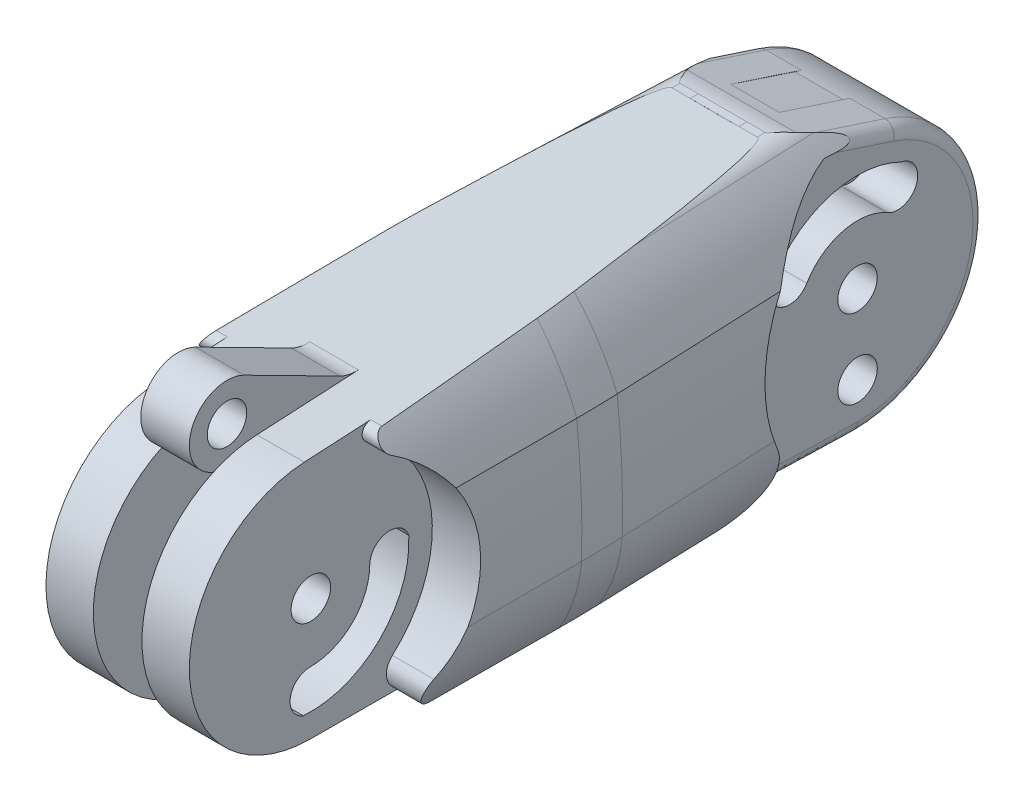
SolidWorks part; units mm, degrees
other "Camera1"
other "Camera2"
ref_plane "Front Plane" through (0, 0, 0) normal (0, 0, 1) x (1, 0, 0)
ref_plane "Top Plane" through (0, 0, 0) normal (0, 1, 0) x (1, 0, 0)
ref_plane "Right Plane" through (0, 0, 0) normal (1, 0, 0) x (0, 0, -1)
sketch "Sketch1" plane through (0, 0, 0) normal (1, 0, 0) x (0, 0, -1)
  line L0 (6.4997, -0.0595) -> (0, 0) construction
  line L1 (0, 0) -> (-0.0595, -6.4997) construction
  line L2 (0, 0) -> (11.6209, -0.1064) construction
  line L3 (39.3989, 2.8894) -> (44.9981, -0.4119) construction
  line L4 (44.9981, -0.4119) -> (48.2995, 5.1872) construction
  line L5 (-0.5384, 9.9855) -> (39.1425, 12.125)
  line L6 (41.3318, 11.8361) -> (48.2642, 9.5672)
  circle A0 centre (0, 0) radius 1.625
  circle A1 centre (44.9981, -0.4119) radius 1.625
  arc A2 (-1.6942, -6.2753) -> (6.3053, 1.579) centre (0, 0) ccw construction
  arc A3 (49.603, 4.1756) -> (38.7481, 1.3732) centre (44.9981, -0.4119) ccw construction
  arc A4 (-0.0444, -4.8498) -> (4.8498, -0.0444) centre (0, 0) ccw
  arc A5 (-0.6238, -8.0502) -> (8.0603, 0.4763) centre (0, 0) ccw
  arc A6 (8.0603, 0.4763) -> (4.8498, -0.0444) centre (6.4997, -0.0595) ccw
  arc A7 (-0.0444, -4.8498) -> (-0.6238, -8.0502) centre (-0.0595, -6.4997) ccw
  arc A8 (47.4615, 3.7659) -> (40.8203, 2.0514) centre (44.9981, -0.4119) ccw
  arc A9 (48.6157, 6.8066) -> (37.7795, 3.2057) centre (44.9981, -0.4119) ccw
  arc A10 (37.7795, 3.2057) -> (40.8203, 2.0514) centre (39.3989, 2.8894) ccw
  arc A11 (47.4615, 3.7659) -> (48.6157, 6.8066) centre (48.2995, 5.1872) ccw
  arc A12 (44.9981, -10.9119) -> (48.2642, 9.5672) centre (44.9981, -0.4119) ccw
  arc A13 (-0.5384, 9.9855) -> (0, -10) centre (0, 0) ccw
  arc A14 (39.1425, 12.125) -> (41.3318, 11.8361) centre (39.4655, 6.1337) cw
  spline S0 degree 3 poles (44.9981, -10.9119) (37.0207, -10.7959) (25.9467, -10) (0, -10) knots 0 0 0 0 1 1 1 1
  point P43 (40.2642, 12.1855)
  dimension "D2" = 3.25
  dimension "D3" = 13
  dimension "D4" = 1.65
  dimension "D5" = 10.5
  dimension "D10" = 20
  dimension "D13" = 6
  dimension "D1" = 45
  dimension "D6" = 90
  dimension "D7" = 0
  dimension "D8" = 90
  dimension "D9" = 30
  dimension "D11" = 2.2
  dimension "D12" = 8
extrude "Boss-Extrude1" add sketch "Sketch1" along normal mid plane 20
sketch "Sketch3" plane through (-10, 0, 0) normal (-1, 0, 0) x (0, 0, 1)
  circle A0 centre (-44.9981, -0.4119) radius 11
  dimension "D1" = 22
extrude "Cut-Extrude1" cut sketch "Sketch3" against normal blind 4.1
mirror "Mirror1" about plane through (0, 0, 0) normal (1, 0, 0) of "Cut-Extrude1"
sketch "Sketch5" plane through (0, 0, 0) normal (1, 0, 0) x (0, 0, -1)
  circle A0 centre (0, 0) radius 10
  dimension "D1" = 20
extrude "Cut-Extrude3" cut sketch "Sketch5" against normal mid plane 12
sketch "Sketch6" plane through (0, 0, 0) normal (1, 0, 0) x (0, 0, -1)
  line L20 (39.2501, 10.1279) -> (55.8409, 11.0225)
  line L21 (55.8409, 11.0225) -> (57.0278, -10.9915)
  line L22 (39.2501, 10.1279) -> (-0.4307, 7.9884)
  line L23 (47.6421, 7.6664) -> (40.7097, 9.9353)
  line L24 (39.2501, 10.1279) -> (-0.4307, 7.9884)
  line L26 (57.0278, -10.9915) -> (-8, -10.9915)
  line L27 (-8, -10.9915) -> (-8, 0)
  arc A6 (40.7097, 9.9353) -> (39.2501, 10.1279) centre (39.4655, 6.1337) ccw
  arc A7 (45.0119, -8.9119) -> (47.6421, 7.6664) centre (44.9981, -0.4119) ccw
  arc A8 (-0.4307, 7.9884) -> (0, -8) centre (0, 0) ccw
  arc A11 (-0.4307, 7.9884) -> (-8, 0) centre (0, 0) ccw
  spline S8 degree 3 poles (-629.4347, 769.0527) (-440.0939, -94.2718) (-207.9713, -3.0744) (26.2611, -8.3178) (30.0115, -8.4293) (35.6362, -8.6246) (37.5109, -8.6944) (99.686, -10.84) (160.1173, -8.7801) (251.4508, 969.4985) knots -14.861079 -14.861079 -14.861079 -14.861079 0.5 0.5 0.75 0.75 0.875 0.875 4.89518 4.89518 4.89518 4.89518 only from (0, -8) to (45.0119, -8.9119)
  dimension "D1" = 2
extrude "Cut-Extrude4" cut sketch "Sketch6" against normal mid plane 4
sketch "Sketch10" plane through (0, 0, 0) normal (0, 0, 1) x (1, 0, 0)
  line L0 (0, 12.123) -> (-4.3435, 12.1247)
  line L9 (10, 12.125) -> (-10, 12.125) construction
  line L11 (-7.5, -11) -> (-12.998, -11)
  line L12 (-12.998, -11) -> (-12.998, 14.3465)
  line L13 (-12.998, 14.3465) -> (0, 14.3465)
  line L14 (0, 14.3465) -> (0, 12.123)
  arc A2 (-5.8246, 11.4695) -> (-9.5, 5.5) centre (8.2393, -1.3058) ccw
  arc A3 (-9.5, 5.5) -> (-9.9, -4.5) centre (70.0795, -2.6912) ccw
  arc A4 (-9.9, -4.5) -> (-7.5, -11) centre (3.0542, -3.41) ccw
  arc A5 (-4.3435, 12.1247) -> (-5.8246, 11.4695) centre (-4.3442, 10.1247) ccw
  point P14 (-10, 9.9855)
  point P22 (-5.2, 12.125)
  dimension "D2" = 5.5
  dimension "D1" = 5.2
  dimension "D4" = 19
  dimension "D7" = 80
  dimension "D10" = 13
  dimension "D11" = 2
  dimension "D3" = 9.5
  dimension "D5" = 9.9
  dimension "D6" = 4.5
  dimension "D8" = 7.5
  dimension "D9" = 11
  dimension "D12" = 9.9
sketch "Sketch20" plane through (0, 0, 0) normal (0, 1, 0) x (1, 0, 0)
  line L0 (-10, -10) -> (-10, 18.2865)
  line L1 (-10, 39.1425) -> (-10, -0.5384) construction
  line L2 (-9.9266, 21.7119) -> (-8.5, 55)
  arc A0 (-10, 18.2865) -> (-9.9266, 21.7119) centre (70, 18.2865) cw
  point P9 (-10, 20)
  dimension "D4" = 80
  dimension "D1" = 1.5
  dimension "D2" = 20
  dimension "D3" = 55
sweep "Sweep1" add profiles "Sketch10" path "Sketch20"
mirror "Mirror4" about plane through (0, 14.3465, -18.2865) normal (1, 0, 0) of bodies 117
combine bodies "Combine2" operation type subtract main body 107 bodies to subtract 120 117
sketch "Sketch15" plane through (-6, 0, 0) normal (1, 0, 0) x (0, 0, -1)
  circle A0 centre (0, 0) radius 1.625 construction
  circle A1 centre (0, 0) radius 1.625
  arc A2 (-0.0444, -4.8498) -> (-0.6238, -8.0502) centre (-0.0595, -6.4997) ccw construction
  arc A3 (0, -10) -> (-0.5384, 9.9855) centre (0, 0) ccw
  arc A5 (0, -10) -> (-0.5384, 9.9855) centre (0, 0) ccw
  arc A8 (8.0603, 0.4763) -> (4.8498, -0.0444) centre (6.4997, -0.0595) ccw construction
  arc A9 (-0.0444, -4.8498) -> (4.8498, -0.0444) centre (0, 0) ccw construction
  arc A14 (-0.6238, -8.0502) -> (8.0603, 0.4763) centre (0, 0) ccw construction
  arc A15 (-0.5384, 9.9855) -> (0, -10) centre (0, 0) ccw
  arc A17 (-0.0444, -4.8498) -> (-0.6238, -8.0502) centre (-0.0595, -6.4997) ccw
  arc A18 (8.0603, 0.4763) -> (4.8498, -0.0444) centre (6.4997, -0.0595) ccw
  arc A19 (-0.0444, -4.8498) -> (4.8498, -0.0444) centre (0, 0) ccw
  arc A20 (-0.6238, -8.0502) -> (8.0603, 0.4763) centre (0, 0) ccw
  arc A21 (-0.5384, 9.9855) -> (0, -10) centre (0, 0) ccw
  dimension "D1" = 0
extrude "Boss-Extrude3" add sketch "Sketch15" along normal blind 4
sketch "Sketch19" plane through (-5.9, 0, 0) normal (-1, 0, 0) x (0, 0, 1)
  circle A0 centre (0, 0) radius 10
  circle A1 centre (0, 0) radius 1.625
  arc A2 (-4.8498, -0.0444) -> (-8.0603, 0.4763) centre (-6.4997, -0.0595) ccw construction
  arc A3 (-8.0603, 0.4763) -> (0.6238, -8.0502) centre (0, 0) ccw construction
  arc A4 (0.6238, -8.0502) -> (0.0444, -4.8498) centre (0.0595, -6.4997) ccw construction
  arc A5 (-4.8498, -0.0444) -> (0.0444, -4.8498) centre (0, 0) ccw construction
  arc A6 (-4.8498, -0.0444) -> (-8.0603, 0.4763) centre (-6.4997, -0.0595) ccw
  arc A7 (-8.0603, 0.4763) -> (0.6238, -8.0502) centre (0, 0) ccw
  circle A14 centre (0, 0) radius 1.625
  arc A15 (0.6238, -8.0502) -> (0.0444, -4.8498) centre (0.0595, -6.4997) ccw
  arc A16 (-4.8498, -0.0444) -> (0.0444, -4.8498) centre (0, 0) ccw
  dimension "D2" = 20
  dimension "D3" = 0
extrude "Cut-Extrude6" cut sketch "Sketch19" along normal through all
mirror "Mirror2" about plane through (0, 0, 0) normal (1, 0, 0) of "Boss-Extrude3", "Cut-Extrude6"
fillet "Fillet7" radius 3.5 2 edges at (-6.2997, -10.8282, -41.4623) (6.2997, -10.8282, -41.4623)
fillet "Fillet4" radius 0.75 4 edges at (0, 10.4659, -45.5183) (0, 9.9855, 0.5384) (6.4708, 9.9855, 0.5384) (-6.4708, 9.9855, 0.5384)
sketch "Sketch9" plane through (0, 0, 0) normal (1, 0, 0) x (0, 0, -1)
  line L0 (10.3218, 10.5711) -> (8.9733, 9.094)
  line L2 (18.2865, 11.0005) -> (4.9309, 10.2804) construction
  line L3 (8.9733, 9.094) -> (0.0454, 8.0357)
  line L4 (-1.2399, 8.1633) -> (-3.9631, 9.0534)
  line L5 (6.2909, 10.7568) -> (-1.5958, 14.7637)
  line L6 (10.3218, 10.5711) -> (7.8113, 10.4357)
  circle A0 centre (-3, 12) radius 1.625
  arc A1 (-1.5958, 14.7637) -> (-3.9631, 9.0534) centre (-3, 12) ccw
  arc A3 (0.0454, 8.0357) -> (-1.2399, 8.1633) centre (-0.3078, 11.0148) cw
  arc A4 (6.2909, 10.7568) -> (7.8113, 10.4357) centre (7.6497, 13.4313) ccw
  point P20 (0, 7.0104)
  dimension "D1" = 3.25
  dimension "D2" = 6.2
  dimension "D4" = 3
  dimension "D5" = 3
  dimension "D6" = 12
  dimension "D3" = 3
  dimension "D7" = 2
extrude "Boss-Extrude2" add sketch "Sketch9" along normal mid plane 4
sketch "Sketch16" plane through (-5.9, 0, 0) normal (-1, 0, 0) x (0, 0, 1)
  line L0 (-44.9981, -0.4119) -> (-39.3989, 2.8894) construction
  line L1 (-44.9981, -0.4119) -> (-44.9981, -6.9119) construction
  circle A2 centre (-44.9981, -6.9119) radius 1.625
  dimension "D1" = 6.5
  dimension "D2" = 3.25
extrude "Cut-Extrude5" cut sketch "Sketch16" against normal through all
fillet "Fillet6" radius 1.5 2 edges at (-7.0258, -10, 0) (7.0258, -10, 0)
sketch "Sketch21" plane through (-2, 0, 0) normal (1, 0, 0) x (0, 0, -1)
  line L0 (41.5183, 10.2502) -> (5.5606, 8.3114) construction
  line L1 (41.5183, 10.2502) -> (39.1364, 10.1218) construction
  line L3 (39.1364, 12.1247) -> (39.1364, 10.1218)
  line L5 (54.9786, -0.8921) -> (55.0785, -0.897)
  line L6 (47.7375, 9.7244) -> (42.452, 11.4695)
  line L7 (39.7945, 12.1247) -> (39.1364, 12.1247) construction
  line L8 (42.452, 11.4695) -> (41.3318, 11.8361) construction
  line L9 (39.7945, 12.1247) -> (39.1364, 12.1247)
  line L10 (42.452, 11.4695) -> (41.3318, 11.8361)
  arc A0 (54.5978, -0.4894) -> (48.7792, 8.4121) centre (44.9981, -0.4119) ccw
  arc A2 (44.9981, -10.9119) -> (48.2642, 9.5672) centre (44.9981, -0.4119) ccw construction
  arc A3 (41.3318, 11.8361) -> (39.7945, 12.1247) centre (39.4655, 6.1337) ccw construction
  arc A4 (55.4977, -0.5008) -> (47.7375, 9.7244) centre (44.9981, -0.4119) ccw
  arc A5 (39.1364, 10.1218) -> (48.7792, 8.4121) centre (40.2961, -11.3853) cw
  arc A6 (55.0785, -0.897) -> (55.4977, -0.5008) centre (55.0978, -0.4974) ccw
  arc A7 (54.9786, -0.8921) -> (54.5978, -0.4894) centre (54.9978, -0.4926) cw
  arc A8 (41.3318, 11.8361) -> (39.7945, 12.1247) centre (39.4655, 6.1337) ccw
  point P25 (54.587, -0.8733)
  dimension "D1" = 19.2
  dimension "D3" = 0.4
fillet "Fillet9" radius 1 6 edges at (5.9, -2.0656, -55.3671) (-5.9, -2.0656, -55.3671) (5.9, 9.7619, -47.6694) (-5.9, 9.7619, -47.6694)
extrude "Boss-Extrude4" add sketch "Sketch21" along normal blind 4
